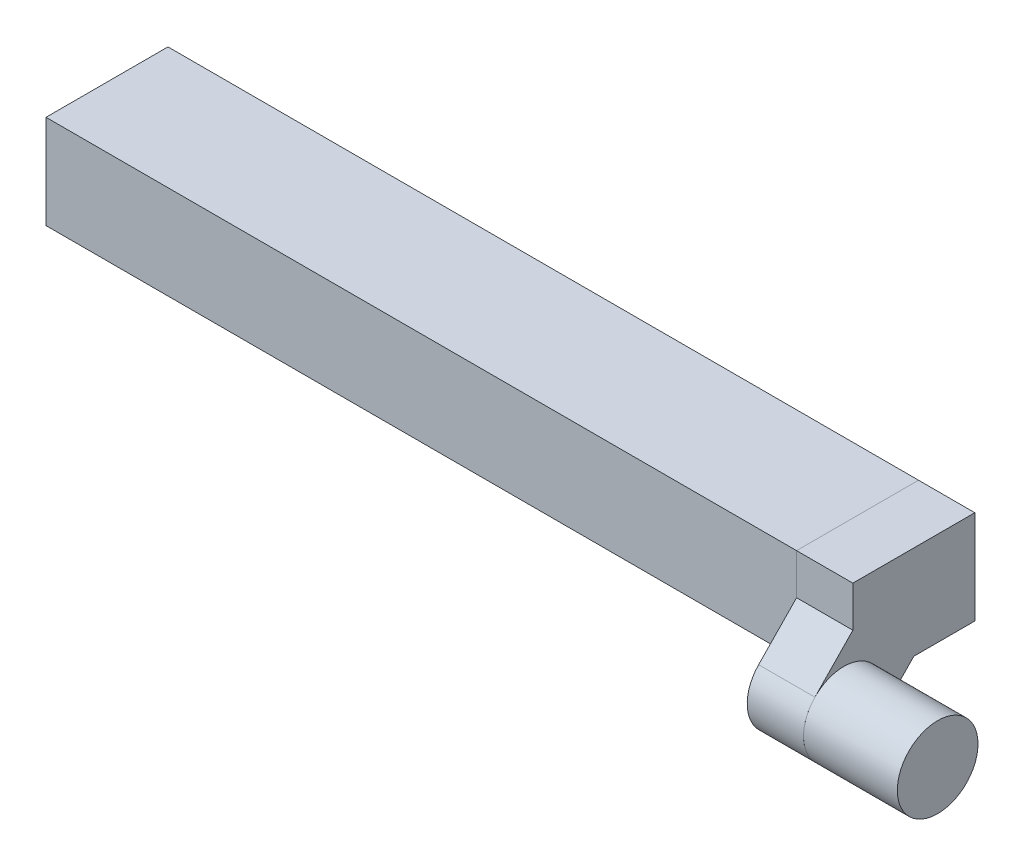
SolidWorks part; units mm, degrees
ref_plane "Front Plane" through (0, 0, 0) normal (0, 0, 1) x (1, 0, 0)
ref_plane "Top Plane" through (0, 0, 0) normal (0, 1, 0) x (1, 0, 0)
ref_plane "Right Plane" through (0, 0, 0) normal (1, 0, 0) x (0, 0, -1)
sketch "Sketch2" plane through (0, 0, 0) normal (1, 0, 0) x (0, 0, -1)
  line L1 (-2.05, -2.05) -> (2.05, -2.05)
  line L2 (-2.05, -2.05) -> (-2.05, 2.05)
  line L3 (-2.05, 2.05) -> (2.05, 2.05)
  line L4 (2.05, -2.05) -> (2.05, 2.05)
  line L5 (-2.05, -2.05) -> (2.05, 2.05) construction
  line L6 (-2.05, 2.05) -> (2.05, -2.05) construction
  line L7 (3.25, -2.5) -> (-3.25, -2.5)
  line L8 (3.25, -2.5) -> (3.25, 2.5)
  line L9 (3.25, 2.5) -> (-3.25, 2.5)
  line L10 (-3.25, -2.5) -> (-3.25, 2.5)
  line L11 (3.25, -2.5) -> (-3.25, 2.5) construction
  line L12 (3.25, 2.5) -> (-3.25, -2.5) construction
  point P0 (0, 0)
  point P5 (0, 0)
  dimension "D1" = 4.1
  dimension "D2" = 4.1
  dimension "D3" = 6.5
  dimension "D4" = 5
extrude "Boss-Extrude1" add sketch "Sketch2" along normal blind 10
extrude "Boss-Extrude2" add sketch "Sketch2<2>" along normal blind 25 from offset 15 contours L1 L4 L3 L2 | L10 L7 L8 L9 L4 L1 L2 L3 region at (0, 0, 0) region at (0, -2.418, 0)
sketch "Sketch2<2>" plane through (0, 0, 0) normal (1, 0, 0) x (0, 0, -1) same geometry as "Sketch2"
sketch "Sketch5" plane through (40, 0, 0) normal (1, 0, 0) x (0, 0, -1)
  line L6 (-3.25, 2.5) -> (3.25, 2.5)
  line L7 (3.25, 2.5) -> (3.25, -2.5)
  line L8 (3.25, -2.5) -> (0, -2.5)
  line L9 (-3.25, -2.5) -> (3.25, -2.5) construction
  line L10 (0, -2.5) -> (-2.189, -4.7517)
  line L11 (-5.2722, -1.7543) -> (-3.25, 0.3257)
  line L12 (-3.25, -2.5) -> (-3.25, 2.5) construction
  line L13 (-5.2722, -1.7543) -> (-2.189, -4.7517) construction
  line L14 (-3.25, 0.3257) -> (-3.25, 2.5)
  arc A1 (-5.2722, -1.7543) -> (-2.189, -4.7517) centre (-3.7306, -3.253) ccw
  point P1 (3.0798, 2.5)
  point P3 (-6.2521, 0.3257)
  dimension "D3" = 5
  dimension "D4" = 4.3
extrude "Boss-Extrude3" add sketch "Sketch5" along normal blind 3
sketch "Sketch6" plane through (43, 0, 0) normal (1, 0, 0) x (0, 0, -1)
  circle A1 centre (-3.7306, -3.253) radius 2.15
  dimension "D1" = 4.3
extrude "Boss-Extrude4" add sketch "Sketch6" along normal blind 5
extrude "Boss-Extrude5" add sketch "Sketch2<4>" along normal blind 5 from offset 10
sketch "Sketch2<4>" plane through (0, 0, 0) normal (1, 0, 0) x (0, 0, -1) same geometry as "Sketch2"
